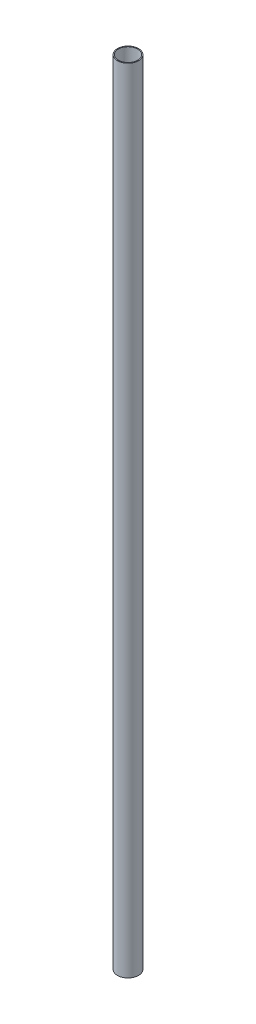
SolidWorks part; units mm, degrees
material "Thornel Mat VMA"
ref_plane "前视基准面" through (0, 0, 0) normal (0, 0, 1) x (1, 0, 0)
ref_plane "上视基准面" through (0, 0, 0) normal (0, 1, 0) x (1, 0, 0)
ref_plane "右视基准面" through (0, 0, 0) normal (1, 0, 0) x (0, 0, -1)
sketch "草图1" plane through (0, 0, 0) normal (0, 1, 0) x (1, 0, 0)
  circle A0 centre (0, 0) radius 5.5
  circle A1 centre (0, 0) radius 6
  dimension "D1" = 12
  dimension "D2" = 0.5
extrude "凸台-拉伸1" add sketch "草图1" along normal blind 450
